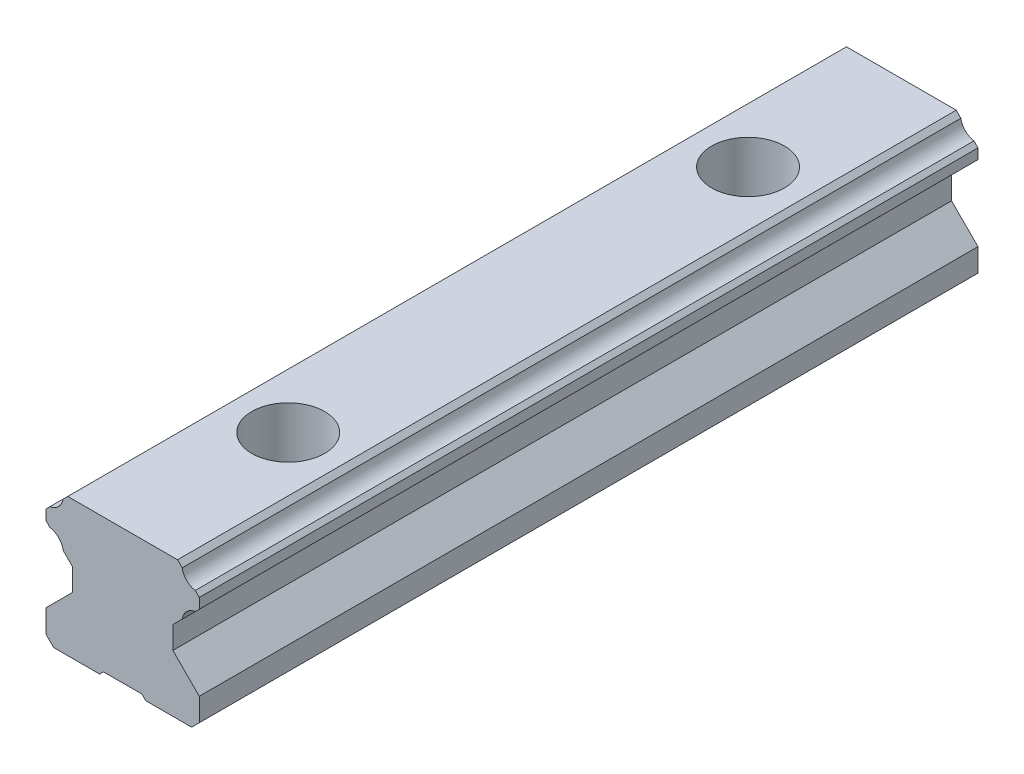
SolidWorks part; units mm, degrees
ref_plane "Front Plane" through (0, 0, 0) normal (0, 0, 1) x (1, 0, 0)
ref_plane "Top Plane" through (0, 0, 0) normal (0, 1, 0) x (1, 0, 0)
ref_plane "Right Plane" through (0, 0, 0) normal (1, 0, 0) x (0, 0, -1)
sketch "Sketch1" plane through (-20, 0, 0) normal (0, 0, 1) x (1, 0, 0)
  line L0 (10, 4.0001) -> (10, 1)
  line L1 (10, 1) -> (11, 0)
  line L2 (11, 0) -> (17, 0)
  line L3 (17, 0) -> (17.5, 0.5)
  line L4 (17.5, 0.5) -> (22.5, 0.5)
  line L5 (26.55, 7.45) -> (30, 4.0001)
  line L6 (26.55, 10.3792) -> (26.55, 7.45)
  line L7 (27.7679, 11.5951) -> (26.55, 10.3792)
  line L8 (30, 13.8292) -> (29.4727, 13.3144)
  line L9 (30, 15.16) -> (30, 13.8292)
  line L10 (29.4727, 15.6874) -> (30, 15.16)
  line L11 (27.16, 18) -> (27.7679, 17.3921)
  line L12 (23, 0) -> (22.5, 0.5)
  line L13 (29, 0) -> (23, 0)
  line L14 (30, 1) -> (29, 0)
  line L15 (30, 4.0001) -> (30, 1)
  line L16 (27.16, 18) -> (12.84, 18)
  line L17 (12.84, 18) -> (12.2321, 17.3921)
  line L18 (10.5273, 15.6874) -> (10, 15.16)
  line L19 (10, 15.16) -> (10, 13.8292)
  line L20 (10, 13.8292) -> (10.5273, 13.3144)
  line L21 (12.2321, 11.5951) -> (13.45, 10.3792)
  line L22 (13.45, 10.3792) -> (13.45, 7.45)
  line L23 (13.45, 7.45) -> (10, 4.0001)
  line L24 (20, 0) -> (20, 0.5) construction
  line L25 (20, 0.5) -> (20, 18) construction
  arc A0 (29.4727, 13.3144) -> (27.7679, 11.5951) centre (29.8039, 11.2812) ccw
  arc A1 (27.7679, 17.3921) -> (29.4727, 15.6874) centre (29.8015, 17.7209) ccw
  arc A2 (12.2321, 17.3921) -> (10.5273, 15.6874) centre (10.1985, 17.7209) cw
  arc A3 (10.5273, 13.3144) -> (12.2321, 11.5951) centre (10.1961, 11.2812) cw
  dimension "D17" = 2.06
  dimension "D1" = 20
  dimension "D2" = 1
  dimension "D3" = 1
  dimension "D4" = 0.5
  dimension "D5" = 0.5
  dimension "D6" = 6
  dimension "D7" = 18
  dimension "D8" = 4.0001
  dimension "D9" = 10.55
  dimension "D10" = 13.1001
  dimension "D11" = 15.5359
  dimension "D12" = 0.6079
  dimension "D13" = 0.6079
  dimension "D14" = 17.5
  dimension "D15" = 0.5273
  dimension "D16" = 0.5273
  dimension "D18" = 1.2159
  dimension "D19" = 0.5148
  dimension "D20" = 6.4049
  dimension "D21" = 2.84
  dimension "D22" = 4.1708
extrude "Extrude1" add sketch "Sketch1" against normal blind 220
sketch "Sketch2" plane through (0, 0, 0) normal (1, 0, 0) x (0, 0, -1)
  line L0 (20, 18) -> (24.75, 18)
  line L1 (24.75, 18) -> (24.75, 9.5)
  line L2 (24.75, 9.5) -> (23, 9.5)
  line L3 (23, 9.5) -> (23, 0)
  line L4 (23, 0) -> (20, 0)
  line L5 (20, 0) -> (20, 18) construction
  line L6 (20, 0) -> (20, 18) construction
  line L7 (220, 0) -> (0, 0) construction
  line L8 (220, 18) -> (0, 18) construction
  line L9 (20, 18) -> (20, 0)
  dimension "D1" = 9.5
  dimension "D2" = 8.5
  dimension "D3" = 6
  dimension "D4" = 20
revolve "Cut-Revolve1" cut sketch "Sketch2" angle 360 about L6 reverse direction yes
ref_axis "Axis1" through (0, 0, -168) along (0, 0, 1)
pattern_linear "LPattern1" count 4 spacing 60 along (0, 0, -1) of "Cut-Revolve1"
ref_plane "Plane1" through (7.7679, 17.3921, 0) normal (0, 0, 1) x (1, 0, 0)
sketch "Sketch3" plane through (7.7679, 17.3921, 0) normal (0, 0, 1) x (1, 0, 0)
  circle A0 centre (-44.089, 19.6981) radius 82.3492
extrude "Cut-Extrude1" cut sketch "Sketch3" against normal blind 118.3996 contours A0
